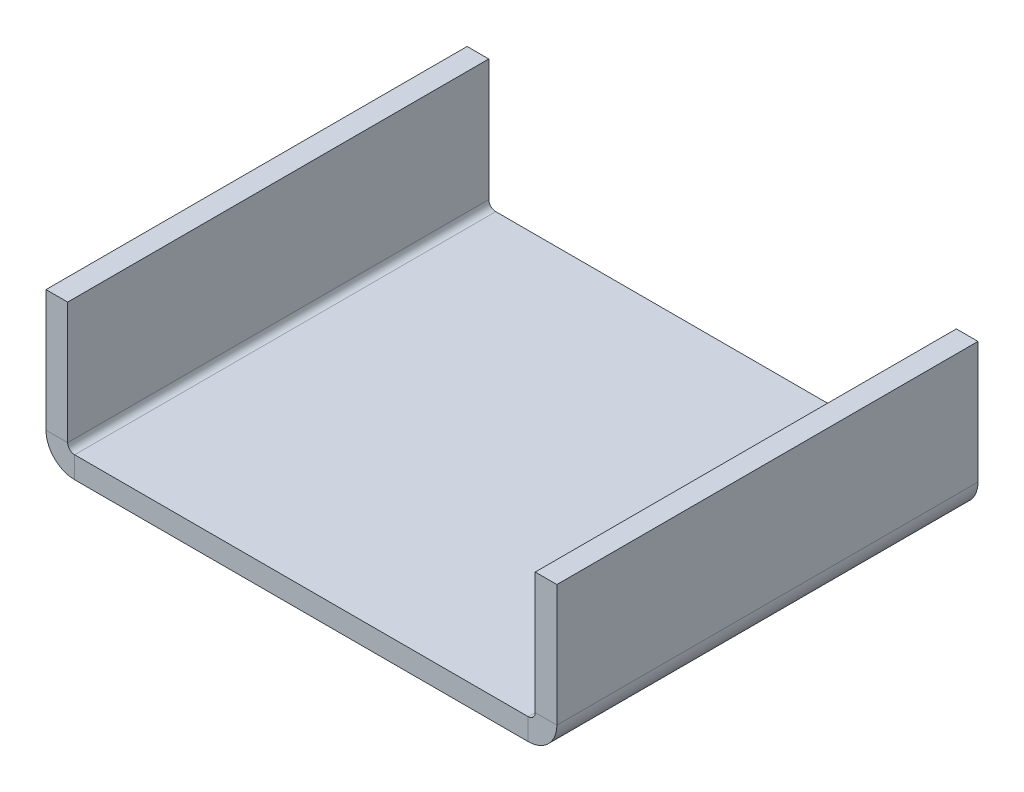
SolidWorks part; units mm, degrees
note: The reader was unsure of these and kept them because the rebuilt part matched: thickness of "Base-Flange2", "Edge-Flange1", "Sheet-Metal2", "Sheet-Metal3"; flange length of "Edge-Flange1".
ref_plane "Front Plane" through (0, 0, 0) normal (0, 0, 1) x (1, 0, 0)
ref_plane "Top Plane" through (0, 0, 0) normal (0, 1, 0) x (1, 0, 0)
ref_plane "Right Plane" through (0, 0, 0) normal (1, 0, 0) x (0, 0, -1)
sketch "Sketch1" plane through (0, 0, 0) normal (0, 1, 0) x (1, 0, 0)
  line L5 (-26.9621, -22.225) -> (26.9621, -22.225)
  line L6 (-26.9621, -22.225) -> (-26.9621, 22.225)
  line L7 (-26.9621, 22.225) -> (26.9621, 22.225)
  line L8 (26.9621, -22.225) -> (26.9621, 22.225)
  line L9 (-26.9621, -22.225) -> (26.9621, 22.225) construction
  line L10 (-26.9621, 22.225) -> (26.9621, -22.225) construction
  point P0 (0, 0)
  dimension "D1" = 53.9242
  dimension "D2" = 44.45
base flange "Base-Flange2" sketch "Sketch1" thickness 2.286 reverse thickness direction no parameters "D1"=0.7366
edge flange "Edge-Flange1" sketch "Sketch14" flange profiles "Sketch14", "Sketch15" flange angle 90 flange length 15.875 flange position material inside bend radius 0.7366 thickness 2.286 relief rectangular parameters "D6"=10, "D8"=0.254
sketch "Sketch14" plane through (-26.9621, 0, 0) normal (-1, 0, 0) x (0, 0, 1)
  line L2 (-22.225, 0) -> (-22.225, 13.589)
  line L3 (-22.225, 13.589) -> (22.225, 13.589)
  line L4 (22.225, 13.589) -> (22.225, 0)
  line L31 (-22.225, 0) -> (22.225, 0) construction
  line L32 (-22.225, 0) -> (22.225, 0)
sketch "Sketch15" plane through (26.9621, 0, 0) normal (1, 0, 0) x (0, 0, -1)
  line L0 (-22.225, 0) -> (22.225, 0) construction
  line L1 (-22.225, 0) -> (22.225, 0)
  line L2 (-22.225, 0) -> (-22.225, 13.589)
  line L3 (-22.225, 13.589) -> (22.225, 13.589)
  line L4 (22.225, 13.589) -> (22.225, 0)
bend "EdgeBend1" bend radius 0.7366 bend angle 90 parameters "D5"=1
bend "EdgeBend2" bend radius 0.7366 bend angle 90 parameters "D5"=2
sketch "Bend-Lines3" [suppressed] plane through (0, 0, 0) normal (0, 1, 0) x (1, 0, 0)
sketch "Bounding-Box3" [suppressed] plane through (0, 0, 0) normal (0, 1, 0) x (1, 0, 0)
sheet metal parameters "Sheet-Metal2" thickness 2.286 parameters "D1"=0.7366
flat pattern "Flat-Pattern2" [suppressed]
sketch "Bend-Lines4" plane through (0, 0, 0) normal (0, 1, 0) x (1, 0, 0)
sketch3d "Bounding-Box4" [suppressed]
  line L0 (26.9621, -31.75, 0) -> (26.9621, 31.75, 0) construction
  line L1 (-26.9621, -31.75, 0) -> (-26.9621, 31.75, 0) construction
  line L2 (26.9621, -31.75, 0) -> (-26.9621, -31.75, 0) construction
  line L3 (26.9621, 31.75, 0) -> (-26.9621, 31.75, 0) construction
sheet metal parameters "Sheet-Metal3" thickness 2.286 parameters "D1"=0.7366
flat pattern "Flat-Pattern2"
sketch "Bend-Lines4" plane through (0, 0, 0) normal (0, 1, 0) x (1, 0, 0)
  line L0 (36.6395, -22.225) -> (36.6395, 22.225) construction
  line L1 (-36.6395, 22.225) -> (-36.6395, -22.225) construction
  line L2 (36.6395, -22.225) -> (36.6395, 22.225) construction
  line L3 (-36.6395, 22.225) -> (-36.6395, -22.225) construction
sketch3d "Bounding-Box4" [suppressed]
  line L0 (62.1919, 22.225, 0) -> (-62.1919, 22.225, 0) construction
  line L1 (62.1919, -22.225, 0) -> (-62.1919, -22.225, 0) construction
  line L2 (62.1919, 22.225, 0) -> (62.1919, -22.225, 0) construction
  line L3 (-62.1919, 22.225, 0) -> (-62.1919, -22.225, 0) construction
bend of the flat pattern "Flatten-<EdgeBend1>1"
bend of the flat pattern "Flatten-<EdgeBend2>1"
